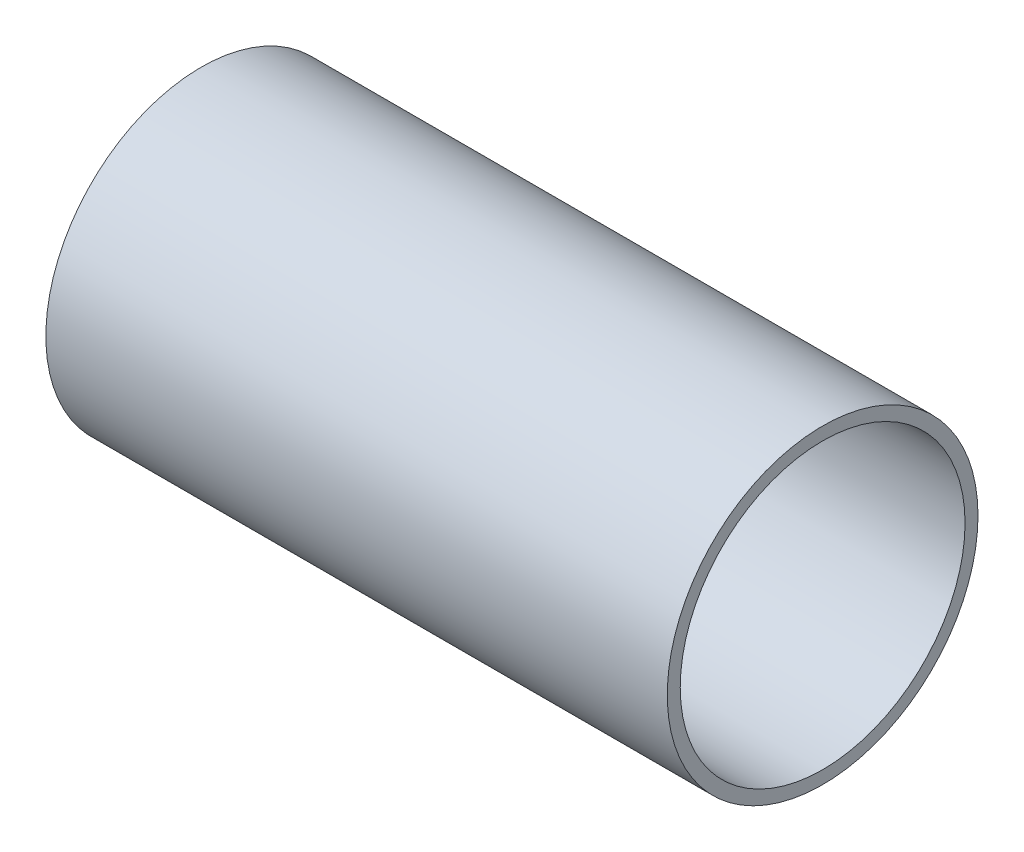
SolidWorks part; units mm, degrees
material "Acrylic (Medium-high impact)"
ref_plane "Front Plane" through (0, 0, 0) normal (0, 0, 1) x (1, 0, 0)
ref_plane "Top Plane" through (0, 0, 0) normal (0, 1, 0) x (1, 0, 0)
ref_plane "Right Plane" through (0, 0, 0) normal (1, 0, 0) x (0, 0, -1)
sketch "Sketch1" plane through (0, 0, 0) normal (1, 0, 0) x (0, 0, -1)
  circle A0 centre (0, 0) radius 76.2
  circle A1 centre (0, 0) radius 69.85
extrude "Boss-Extrude1" add sketch "Sketch1" along normal blind 152.4 and the other way blind 152.4
